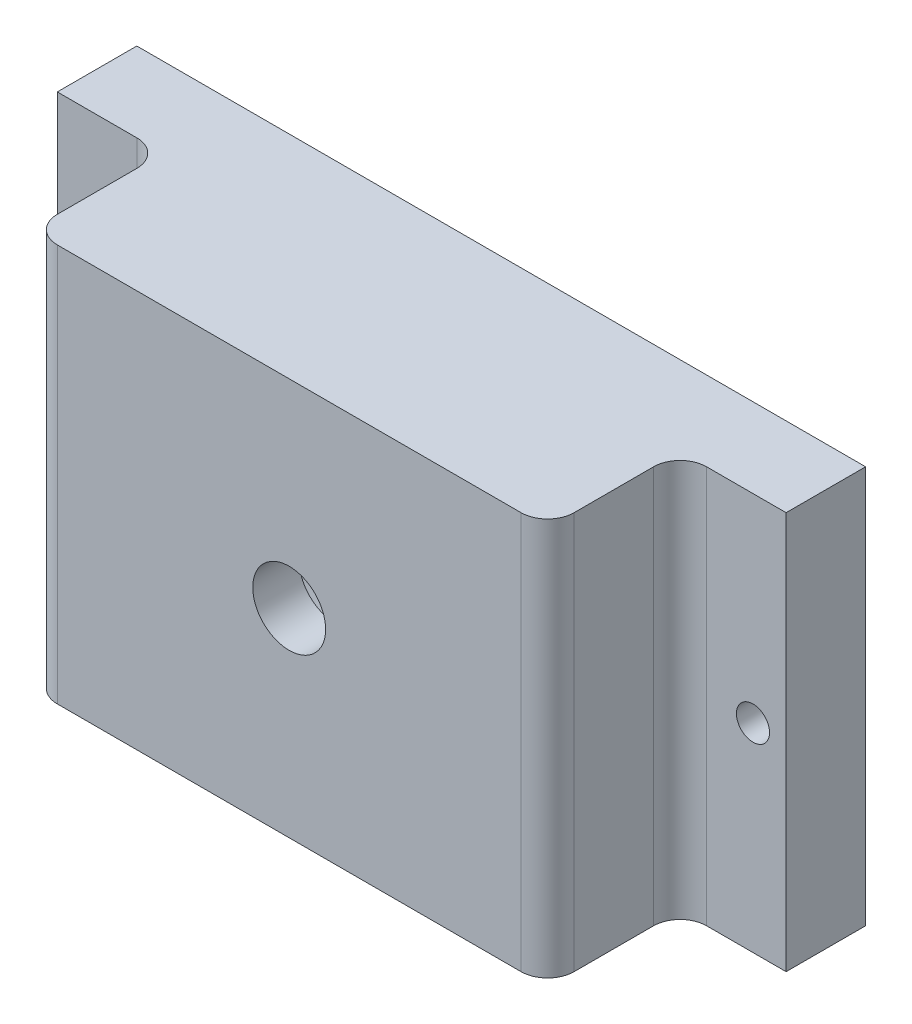
SolidWorks part; units mm, degrees
ref_plane "Front Plane" through (0, 0, 0) normal (0, 0, 1) x (1, 0, 0)
ref_plane "Top Plane" through (0, 0, 0) normal (0, 1, 0) x (1, 0, 0)
ref_plane "Right Plane" through (0, 0, 0) normal (1, 0, 0) x (0, 0, -1)
sketch "Sketch1" plane through (0, 0, 0) normal (0, 0, 1) x (1, 0, 0)
  line L0 (-25, 0) -> (25, 0) construction
  line L1 (-27.5, -15) -> (27.5, -15)
  line L2 (-27.5, -15) -> (-27.5, 15)
  line L3 (-27.5, 15) -> (27.5, 15)
  line L4 (27.5, -15) -> (27.5, 15)
  line L5 (-27.5, -15) -> (27.5, 15) construction
  line L6 (-27.5, 15) -> (27.5, -15) construction
  circle A0 centre (-25, 0) radius 1.25
  circle A1 centre (25, 0) radius 1.25
  point P0 (0, 0)
  point P11 (0, 0)
  point P14 (0, 0)
  dimension "D3" = 2.5
  dimension "D1" = 30
  dimension "D2" = 55
  dimension "D4" = 50
extrude "Main" add sketch "Sketch1" along normal blind 16
sketch "Sketch2" plane through (0, 0, 0) normal (0, 0, 1) x (1, 0, 0)
  line L0 (-27.5, -15) -> (27.5, 15) construction
  line L1 (-27.5, 15) -> (27.5, -15) construction
  circle A0 centre (0, 0) radius 10.3
  point P6 (0, 0)
  point P12 (0, 0)
  dimension "D1" = 20.6
extrude "CentralHole" cut sketch "Sketch2" along normal blind 12.5
sketch "Sketch5" plane through (0, 0, 16) normal (0, 0, 1) x (1, 0, 0)
  line L0 (27.5, 15) -> (-27.5, 15) construction
  line L1 (27.5, -15) -> (19.5, -15)
  line L2 (27.5, -15) -> (27.5, 15)
  line L3 (27.5, 15) -> (19.5, 15)
  line L4 (19.5, -15) -> (19.5, 15)
  line L6 (-27.5, -15) -> (-19.5, -15)
  line L7 (-27.5, -15) -> (-27.5, 15)
  line L8 (-27.5, 15) -> (-19.5, 15)
  line L9 (-19.5, -15) -> (-19.5, 15)
  circle A0 centre (0, 0) radius 2.75
  dimension "D3" = 5.5
  dimension "D1" = 8
  dimension "D2" = 8
extrude "Cut-Extrude3" cut sketch "Sketch5" against normal blind 10
fillet "Fillet1" radius 2 4 edges at (-19.5, 0, 16) (19.5, 0, 16) (-19.5, 0, 6) (19.5, 0, 6)
